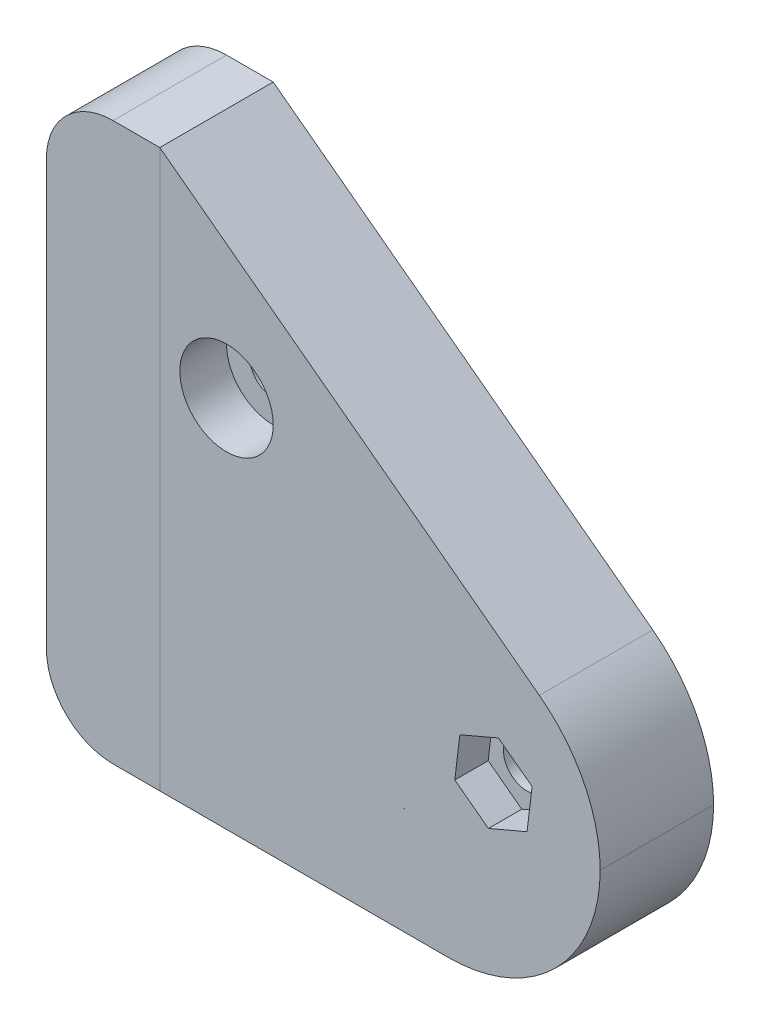
SolidWorks part; units mm, degrees
ref_plane "Front Plane" through (0, 0, 0) normal (0, 0, 1) x (1, 0, 0)
ref_plane "Top Plane" through (0, 0, 0) normal (0, 1, 0) x (1, 0, 0)
ref_plane "Right Plane" through (0, 0, 0) normal (1, 0, 0) x (0, 0, -1)
sketch "Sketch1" plane through (0, 0, 0) normal (0, 0, 1) x (1, 0, 0)
  line L5 (0, -14) -> (-20, 1) construction
  line L37 (8, -10) -> (8, -27)
  line L38 (-25, -27) -> (-25, 14.75)
  line L41 (-25, 14.75) -> (8, -10)
  line L48 (-25, -27) -> (8, -27)
  line L50 (-6.6879, -19) -> (-6.6667, -19)
  line L52 (-6.6667, -19) -> (-6.6879, -18.9841)
  line L54 (-6.6879, -18.9841) -> (-6.6879, -19)
  circle A1 centre (-20, 1) radius 1.75
  circle A2 centre (0, -14) radius 1.75
  dimension "D6" = 3.5
  dimension "D5" = 8
  dimension "D17" = 19
  dimension "D4" = 8
  dimension "D1" = 15
  dimension "D2" = 5
  dimension "D7" = 14
  dimension "D8" = 20
  dimension "D9" = 20
  dimension "D10" = 8
  dimension "D13" = 8
extrude "Boss-Extrude1" add sketch "Sketch1" along normal blind 8.5
sketch "Sketch3" plane through (0, 0, 0) normal (0, 0, -1) x (-1, 0, 0)
  line L0 (25, 14.75) -> (25, -27) construction
  line L1 (22.725, 2.5733) -> (20, 4.1466)
  line L2 (20, 4.1466) -> (17.275, 2.5733)
  line L3 (17.275, 2.5733) -> (17.275, -0.5733)
  line L4 (17.275, -0.5733) -> (20, -2.1466)
  line L5 (20, -2.1466) -> (22.725, -0.5733)
  line L6 (22.725, -0.5733) -> (22.725, 2.5733)
  circle A0 centre (20, 1) radius 2.725 construction
  dimension "D1" = 5.45
extrude "Cut-Extrude2" cut sketch "Sketch3" against normal blind 2.5
sketch "Sketch4" plane through (0, 0, 8.5) normal (0, 0, 1) x (1, 0, 0)
  line L0 (8, -10) -> (-25, 14.75) construction
  line L1 (-2.5172, -12.1121) -> (-2.8936, -15.236)
  line L2 (-2.8936, -15.236) -> (-0.3764, -17.124)
  line L3 (-0.3764, -17.124) -> (2.5172, -15.8879)
  line L4 (2.5172, -15.8879) -> (2.8936, -12.764)
  line L5 (2.8936, -12.764) -> (0.3764, -10.876)
  line L6 (0.3764, -10.876) -> (-2.5172, -12.1121)
  circle A0 centre (0, -14) radius 2.725 construction
  dimension "D1" = 5.45
extrude "Cut-Extrude3" cut sketch "Sketch4" against normal blind 2.5
sketch "Sketch5" plane through (0, 0, 8.5) normal (0, 0, 1) x (1, 0, 0)
  circle A0 centre (-20, 1) radius 3.5
  dimension "D1" = 7
extrude "Cut-Extrude4" cut sketch "Sketch5" against normal blind 3.5
sketch "Sketch6" plane through (0, 0, 0) normal (0, 0, -1) x (-1, 0, 0)
  circle A0 centre (0, -14) radius 3.5
  dimension "D1" = 7
extrude "Cut-Extrude5" cut sketch "Sketch6" against normal blind 3.5
sketch "Sketch7" plane through (-25, 0, 0) normal (-1, 0, 0) x (0, 0, 1)
  line L6 (8.5, -27) -> (0, -27) construction
  line L7 (-0.0008, -27) -> (8.5008, -27)
  line L8 (-0.0008, -27) -> (-0.0008, 14.75)
  line L9 (-0.0008, 14.75) -> (8.5008, 14.75)
  line L10 (8.5008, -27) -> (8.5008, 14.75)
  line L11 (8.5, 14.75) -> (0, 14.75) construction
  point P6 (4.25, -27)
  point P7 (4.25, -27)
  dimension "D1" = 8.5017
fillet "Fillet1" radius 11.4 2 edges at (8, -10, 4.25) (8, -27, 4.25)
extrude "Boss-Extrude3" add sketch "Sketch7" along normal blind 8.5
fillet "Fillet2" radius 5 1 edges at (-33.5, -27, 4.25)
fillet "Fillet3" radius 5 1 edges at (-33.5, 14.75, 4.25)
